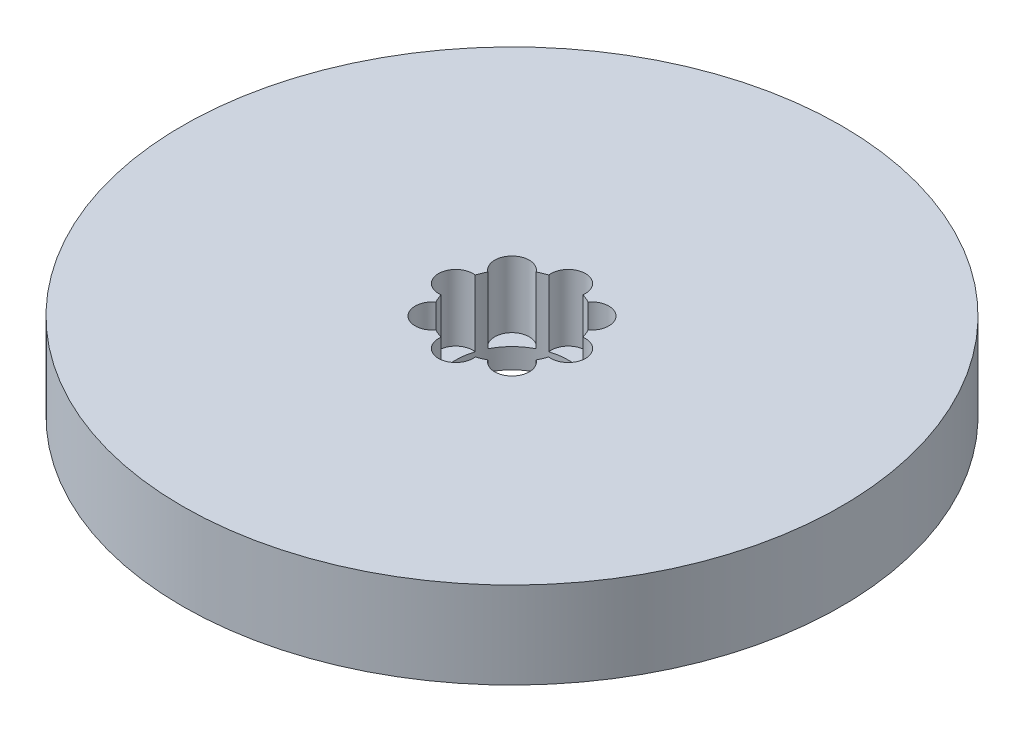
SolidWorks part; units mm, degrees
ref_plane "Front Plane" through (0, 0, 0) normal (0, 0, 1) x (1, 0, 0)
ref_plane "Top Plane" through (0, 0, 0) normal (0, 1, 0) x (1, 0, 0)
ref_plane "Right Plane" through (0, 0, 0) normal (1, 0, 0) x (0, 0, -1)
sketch "Sketch1" plane through (0, 0, 0) normal (0, 1, 0) x (1, 0, 0)
  circle A0 centre (0, 0) radius 87.5
  dimension "FLANGE_OD" = 175
extrude "Boss-Extrude1" add sketch "Sketch1" along normal blind 23
sketch "Sketch2" plane through (0, 0, 0) normal (0, 1, 0) x (1, 0, 0)
  circle A0 centre (0, 0) radius 15
  dimension "BORE_D" = 30
extrude "Cut-Extrude1" cut sketch "Sketch2" along normal through all
sketch "Sketch3" plane through (0, 23, 0) normal (0, 1, 0) x (1, 0, 0)
  circle A0 centre (0, 0) radius 14.9361 construction
  circle A1 centre (-14.9361, 0) radius 4.5827
  dimension "BOLT_D" = 9.1654
  dimension "BOLT_PCD" = 29.8722
extrude "Cut-Extrude2" cut sketch "Sketch3" against normal blind 17.6362
pattern_circular "CirPattern1" count 8 over 360 about axis through (0, 0, 0) along (0, 1, 0) of "Cut-Extrude2"
